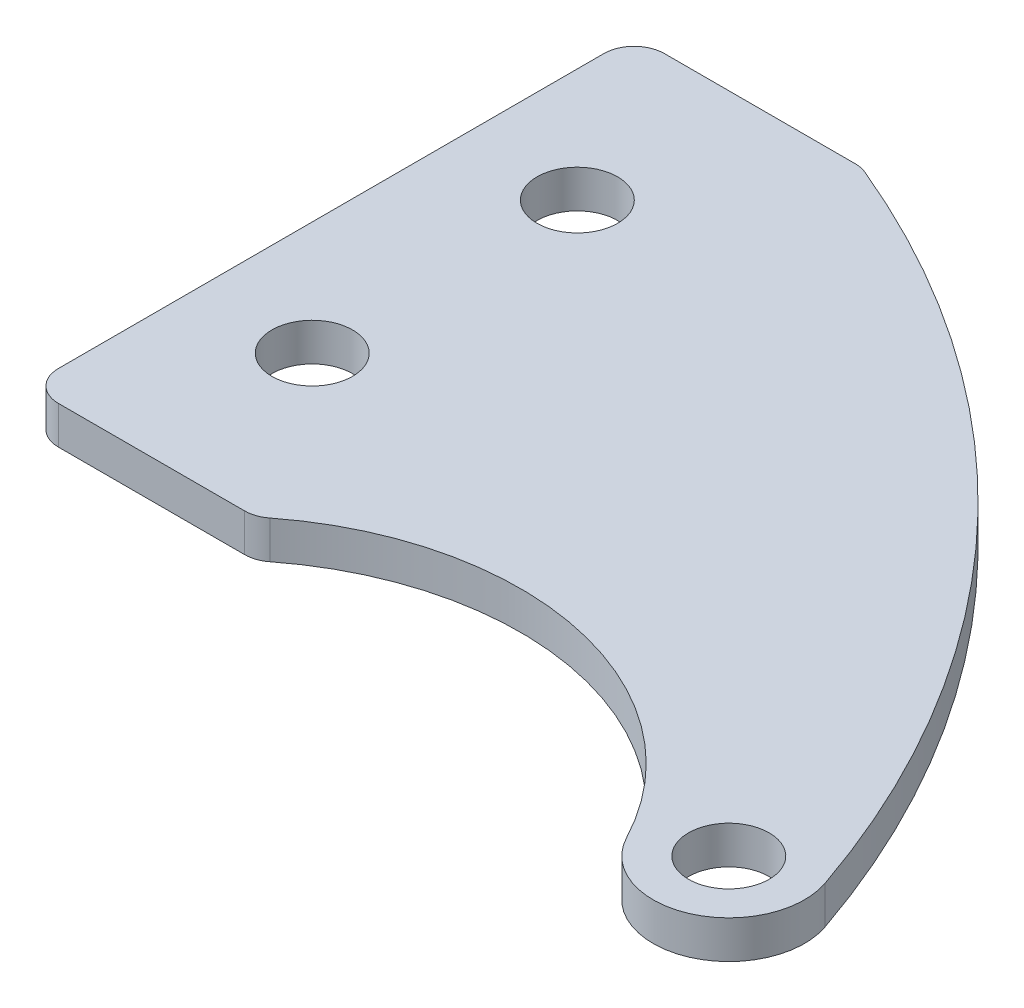
SolidWorks part; units mm, degrees
material "6061-T6 (SS)"
ref_plane "Front" through (0, 0, 0) normal (0, 0, 1) x (1, 0, 0)
ref_plane "Top" through (0, 0, 0) normal (0, 1, 0) x (1, 0, 0)
ref_plane "Right" through (0, 0, 0) normal (1, 0, 0) x (0, 0, -1)
sketch "Sketch1" plane through (0, 0, 0) normal (0, 1, 0) x (1, 0, 0)
  line L1 (0, 50.8) -> (19.05, 50.8)
  line L4 (0, 50.8) -> (0, 0)
  line L6 (0, 0) -> (19.05, 0)
  arc A0 (69.5081, -2.7071) -> (57.8724, -7.704) centre (63.5, -4.7625) cw
  arc A3 (19.05, 0) -> (57.8724, -7.704) centre (35.3619, -19.47) cw
  arc A6 (69.5081, -2.7071) -> (19.05, 50.8) centre (-14.6058, -31.483) ccw
  dimension "D1" = 19.05
  dimension "D2" = 4.7625
  dimension "D3" = 6.35
  dimension "D4" = 63.5
  dimension "D6" = 88.9
  dimension "D7" = 25.4
  dimension "D5" = 50.8
extrude "Boss-Extrude1" add sketch "Sketch1" along normal blind 3.175
hole_wizard "1/4 Clearance Hole2" positions "Sketch4" profile "Sketch3" hole size "1/4" standard "ANSI Inch" end condition through all
sketch "Sketch4" plane through (0, 0, 0) normal (0, -1, 0) x (-1, 0, 0)
  point P0 (-63.5, -4.7625)
sketch "Sketch3" plane through (63.5, 0, 4.7625) normal (1, 0, 0) x (0, 0, -1)
  line L0 (0, 0) -> (0, 3.175)
  line L1 (0, 3.175) -> (3.3782, 3.175)
  line L2 (3.3782, 3.175) -> (3.3782, 0)
  line L5 (3.3782, 0) -> (0, 0)
  line L11 (0, -6.35) -> (0, 107.95) construction
  dimension "Thru Hole Dia." = 6.7564
  dimension "Thru Hole Depth" = 3.175
hole_wizard "1/4 Clearance Hole1" positions "Sketch7" profile "Sketch8" hole size "1/4" standard "ANSI Inch" end condition through all
sketch "Sketch7" plane through (0, 3.175, 0) normal (0, 1, 0) x (1, 0, 0)
  line L9 (9.525, 0) -> (9.525, 14.2875) construction
  line L10 (0, 0) -> (19.05, 0) construction
  line L11 (9.525, 14.2875) -> (9.525, 36.5125) construction
  line L12 (9.525, 36.5125) -> (9.525, 50.8) construction
  line L13 (19.05, 50.8) -> (0, 50.8) construction
  point P0 (9.525, 36.5125)
  point P2 (9.525, 14.2875)
  dimension "D1" = 22.225
sketch "Sketch8" plane through (9.525, 3.175, -36.5125) normal (1, 0, 0) x (0, 0, 1)
  line L0 (0, 0) -> (0, 3.175)
  line L1 (0, 3.175) -> (3.3782, 3.175)
  line L2 (3.3782, 3.175) -> (3.3782, 0)
  line L5 (3.3782, 0) -> (0, 0)
  line L11 (0, -6.35) -> (0, 107.95) construction
  dimension "Thru Hole Dia." = 6.7564
  dimension "Thru Hole Depth" = 3.175
fillet "Fillet1" radius 2.54 4 edges at (19.05, 1.5875, 0) (0, 1.5875, 0) (0, 1.5875, -50.8) (19.05, 1.5875, -50.8)
